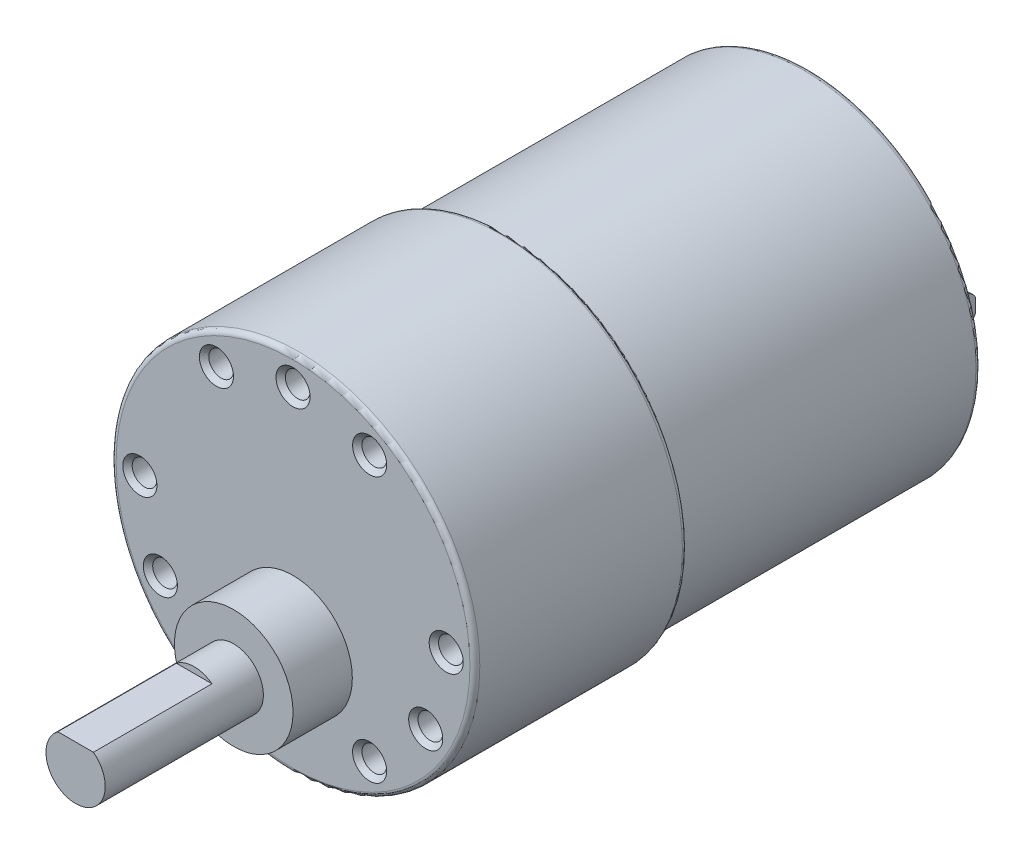
SolidWorks part; units mm, degrees
ref_plane "Front Plane" through (0, 0, 0) normal (0, 0, 1) x (1, 0, 0)
ref_plane "Top Plane" through (0, 0, 0) normal (0, 1, 0) x (1, 0, 0)
ref_plane "Right Plane" through (0, 0, 0) normal (1, 0, 0) x (0, 0, -1)
sketch "Sketch1" plane through (0, 0, 0) normal (0, 0, 1) x (1, 0, 0)
  circle A0 centre (0, 0) radius 18.4
  dimension "D1" = 36.8
extrude "gear box" add sketch "Sketch1" along normal blind 21.5
sketch "Sketch2" plane through (0, 0, 0) normal (0, 0, -1) x (-1, 0, 0)
  circle A0 centre (0, 0) radius 17.4
  dimension "D1" = 34.8
extrude "motor coils" add sketch "Sketch2" along normal blind 30.7
sketch "Sketch3" plane through (0, 0, -30.7) normal (0, 0, -1) x (-1, 0, 0)
  line L0 (0, 20.24) -> (0, -20.24) construction
  circle A0 centre (-11.6123, 0) radius 1.55
  circle A1 centre (11.6123, 0) radius 1.55
  dimension "D1" = 3.1
  dimension "D2" = 11.6123
extrude "Boss-Extrude3" add sketch "Sketch3" along normal blind 0.5
sketch "Sketch4" plane through (0, 0, -31.2) normal (0, 0, -1) x (-1, 0, 0)
  line L1 (-11.8623, 1.45) -> (-11.3623, 1.45)
  line L2 (-11.8623, 1.45) -> (-11.8623, -1.45)
  line L3 (-11.8623, -1.45) -> (-11.3623, -1.45)
  line L4 (-11.3623, 1.45) -> (-11.3623, -1.45)
  line L5 (-11.8623, 1.45) -> (-11.3623, -1.45) construction
  line L6 (-11.8623, -1.45) -> (-11.3623, 1.45) construction
  point P0 (-11.6123, 0)
  dimension "D1" = 0.5
  dimension "D2" = 2.9
extrude "Boss-Extrude4" add sketch "Sketch4" along normal blind 4.5
mirror "Mirror1" about plane through (0, 0, 0) normal (1, 0, 0) of "Boss-Extrude4"
sketch "Sketch6" plane through (11.8623, 0, 0) normal (1, 0, 0) x (0, 0, -1)
  line L0 (32.167, 0) -> (34.6761, 0) construction
  line L1 (20.24, 0) -> (-20.24, 0) construction
  line L2 (32.167, 0.592) -> (34.6761, 0.592)
  line L3 (32.167, -0.592) -> (34.6761, -0.592)
  line L4 (35.7, 1.45) -> (31.2, 1.45) construction
  line L5 (35.7, 1.45) -> (35.7, -1.45) construction
  line L6 (34.7902, 1.45) -> (35.8546, 1.9485)
  line L7 (35.8546, 1.9485) -> (37.86, 0.483)
  line L8 (37.86, 0.483) -> (37.5052, -1.3065)
  line L9 (37.5052, -1.3065) -> (35.1758, -1.8773)
  line L10 (35.1758, -1.8773) -> (34.7902, -1.45)
  line L11 (35.7, -0.6989) -> (35.7, 0.6989)
  arc A0 (32.167, 0.592) -> (32.167, -0.592) centre (32.167, 0) ccw
  arc A1 (34.6761, -0.592) -> (34.6761, 0.592) centre (34.6761, 0) ccw
  spline S0 degree 2 poles (34.7902, 1.45) (35.4004, 1.2613) (35.7, 0.6989) knots 0 0 0 1 1 1
  spline S1 degree 2 poles (34.7902, -1.45) (35.4004, -1.2613) (35.7, -0.6989) knots 0 0 0 1 1 1
  point P5 (33.4215, 0)
extrude "Cut-Extrude1" cut sketch "Sketch6" against normal through all
sketch "Sketch7" plane through (0, 0, -30.7) normal (0, 0, -1) x (-1, 0, 0)
  circle A0 centre (0, 0) radius 3.9
  dimension "D1" = 7.8
extrude "Boss-Extrude5" add sketch "Sketch7" along normal blind 1.6
sketch "Sketch8" plane through (0, 0, 21.5) normal (0, 0, 1) x (1, 0, 0)
  circle A0 centre (0, -7) radius 6
  dimension "D2" = 12
  dimension "D1" = 7
extrude "Boss-Extrude6" add sketch "Sketch8" along normal blind 6
sketch "Sketch9" plane through (0, 0, 27.5) normal (0, 0, 1) x (1, 0, 0)
  circle A0 centre (0, -7) radius 3
  dimension "D1" = 6
extrude "Boss-Extrude7" add sketch "Sketch9" along normal blind 16
sketch "Sketch10" plane through (0, 0, 43.5) normal (0, 0, 1) x (1, 0, 0)
  line L0 (-1.8, -4.6) -> (1.8, -4.6)
  line L1 (0, -10) -> (3, -10) construction
  circle A1 centre (0, -7) radius 3
  arc A2 (1.8, -4.6) -> (-1.8, -4.6) centre (0, -7) ccw
  dimension "D2" = 5.4
  dimension "D1" = 0
extrude "Cut-Extrude2" cut sketch "Sketch10" against normal blind 12
hole_wizard "M3 Tapped Hole1" positions "3DSketch1" profile "Sketch11" tap size "M3" standard "AS"
sketch3d "3DSketch1"
  line L9 (0, 0, 21.5) -> (0, 10.082, 21.5) construction
  line L10 (-7.75, 13.4234, 21.5) -> (7.75, 13.4234, 21.5)
  line L12 (0, 0, 21.5) -> (7.5161, 0, 21.5) construction
  line L15 (-7.75, 13.4234, 21.5) -> (7.75, 13.4234, 21.5)
  line L16 (-7.75, 13.4234, 21.5) -> (-7.75, -13.4234, 21.5)
  line L17 (-7.75, -13.4234, 21.5) -> (7.75, -13.4234, 21.5)
  line L18 (7.75, 13.4234, 21.5) -> (7.75, -13.4234, 21.5)
  circle A1 centre (0, 0, 21.5) radius 15.5
  point P103 (-7.75, 13.4234, 21.5)
  point P107 (7.75, 13.4234, 21.5)
  point P113 (0, 13.4234, 21.5)
  point P911 (7.75, 0, 21.5)
  point P932 (0, 15.5, 21.5)
  point P951 (0, 0, 37)
  dimension "D1" = 15.5
  dimension "D2" = 31
sketch "Sketch11" plane through (0, 15.5, 21.5) normal (1, 0, 0) x (0, -1, 0)
  line L0 (0, 0) -> (0, 5)
  line L1 (0, 5) -> (1.25, 4.2489)
  line L2 (1.25, 4.2489) -> (1.25, 0.475)
  line L3 (1.25, 0.475) -> (1.725, 0)
  line L5 (1.725, 0) -> (0, 0)
  line L6 (-1.25, 0.475) -> (-1.725, 0) construction
  line L10 (0, 5) -> (-1.25, 4.2489) construction
  line L11 (0, -6.35) -> (0, 107.95) construction
  dimension "Tap Drill Dia." = 2.5
  dimension "Tap Drill Depth" = 5
  dimension "Near C'Sink Dia." = 3.45
  dimension "Near C'Sink Angle" = 90
  dimension "Drill Angle" = 118
cosmetic thread "Hole Thread44" parameters "D1"=6, "D2"=3
cosmetic thread "Hole Thread47" parameters "D1"=6, "D2"=3
cosmetic thread "Hole Thread48" parameters "D1"=6, "D2"=3
pattern_circular "CirPattern1" count 3 over 360 about axis through (0, 0, 21.5) along (0, 0, -1) of "M3 Tapped Hole1"
cosmetic thread "Hole Thread49" parameters "D1"=6, "D2"=3
cosmetic thread "Hole Thread50" parameters "D1"=6, "D2"=3
cosmetic thread "Hole Thread51" parameters "D1"=6, "D2"=3
cosmetic thread "Hole Thread52" parameters "D1"=6, "D2"=3
cosmetic thread "Hole Thread53" parameters "D1"=6, "D2"=3
cosmetic thread "Hole Thread54" parameters "D1"=6, "D2"=3
fillet "Fillet1" radius 0.5 4 edges at (18.4, 0, 0) (18.4, 0, 21.5) (-17.4, 0, 0) (-17.4, 0, -30.7)
